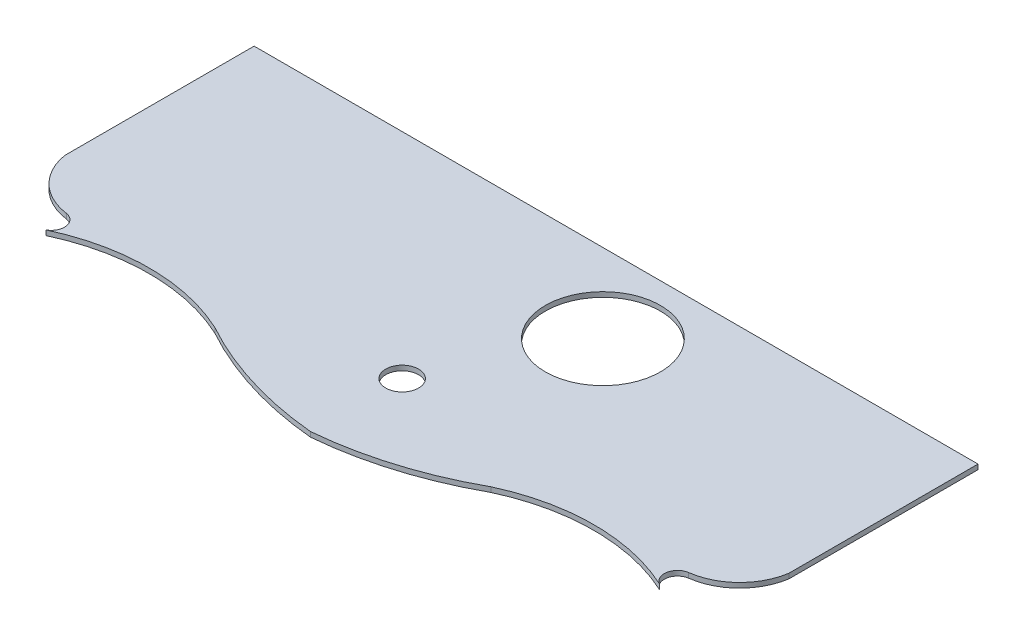
SolidWorks part; units mm, degrees
ref_plane "Front Plane" through (0, 0, 0) normal (0, 0, 1) x (1, 0, 0)
ref_plane "Top Plane" through (0, 0, 0) normal (0, 1, 0) x (1, 0, 0)
ref_plane "Right Plane" through (0, 0, 0) normal (1, 0, 0) x (0, 0, -1)
ref_plane "Plane1" through (0, 4.5, 0) normal (0, 1, 0) x (1, 0, 0)
ref_plane "Plane2" through (0, 3, 0) normal (0, 1, 0) x (1, 0, 0)
sketch "Sketch1" plane through (0, 3, 0) normal (0, 1, 0) x (1, 0, 0)
  line L0 (0, -100) -> (0, 70) construction
  line L5 (-110, 50) -> (-110, -7.5)
  line L18 (0, 0) -> (0, -34.383) construction
  line L19 (-110, 50) -> (110, 50)
  line L22 (110, -7.5) -> (110, 50)
  line L24 (-110, 50) -> (-110, -30) construction
  arc A1 (94.5, -22.5368) -> (93.25, -30) centre (95.1559, -26.4829) ccw
  arc A3 (-110, -7.5) -> (-94.5, -22.5368) centre (-92.222, -4.6815) ccw
  arc A7 (-110, -7.5) -> (-94.5, -22.5368) centre (-92.222, -4.6815) ccw construction
  arc A9 (-94.5, -22.5368) -> (-93.25, -30) centre (-95.1559, -26.4829) cw
  circle A11 centre (0, -15) radius 5
  circle A12 centre (20, 26) radius 17.5
  circle A13 centre (20, 26) radius 17.5 construction
  circle A14 centre (0, -15) radius 5 construction
  arc A15 (-93.25, -30) -> (-94.5, -22.5368) centre (-95.1559, -26.4829) ccw construction
  arc A17 (110, -7.5) -> (94.5, -22.5368) centre (92.222, -4.6815) cw
  arc A18 (93.25, -30) -> (41.9625, -30) centre (67.6063, -85.0296) ccw
  arc A20 (93.25, -30) -> (41.9625, -30) centre (67.6063, -85.0296) ccw construction
  arc A22 (41.9625, -30) -> (0, -42.8761) centre (-9.5248, 62.9793) cw
  arc A23 (0, -42.8761) -> (41.9625, -30) centre (-9.5248, 62.9793) ccw construction
  arc A24 (-41.9625, -30) -> (0, -42.8761) centre (9.5248, 62.9793) ccw
  arc A25 (-41.9625, -30) -> (0, -42.8761) centre (9.5248, 62.9793) ccw construction
  arc A26 (-93.25, -30) -> (-41.9625, -30) centre (-67.6063, -85.0296) cw
  arc A27 (-41.9625, -30) -> (-93.25, -30) centre (-67.6063, -85.0296) ccw construction
extrude "Boss-Extrude1" add sketch "Sketch1" along normal up to surface (1.5 mm away) contours L19 L5 A11 A12 region at (-1.1702, 3, -9.0606)
